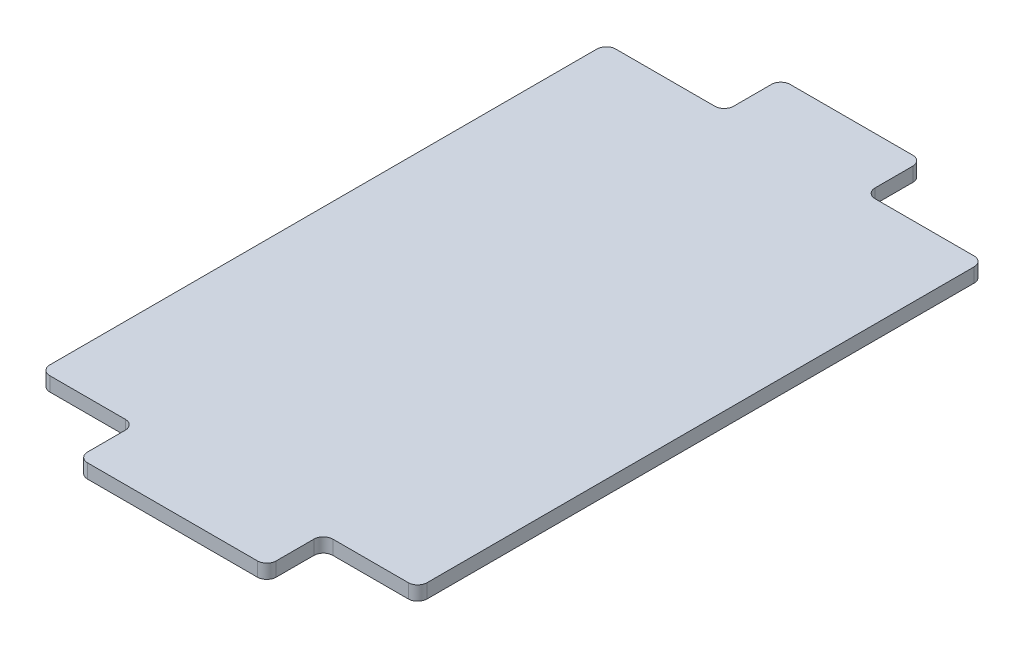
SolidWorks part; units mm, degrees
ref_plane "Спереди" through (0, 0, 0) normal (0, 0, 1) x (1, 0, 0)
ref_plane "Сверху" through (0, 0, 0) normal (0, 1, 0) x (1, 0, 0)
ref_plane "Справа" through (0, 0, 0) normal (1, 0, 0) x (0, 0, -1)
sketch "Эскиз1" plane through (0, 0, 0) normal (0, 1, 0) x (1, 0, 0)
  line L1 (-20, 30) -> (20, 30)
  line L2 (-20, 30) -> (-20, -30)
  line L3 (-20, -30) -> (20, -30)
  line L4 (20, 30) -> (20, -30)
  line L5 (-20, 30) -> (20, -30) construction
  line L6 (-20, -30) -> (20, 30) construction
  point P0 (0, 0)
  dimension "D1" = 60
  dimension "D2" = 40
extrude "Бобышка-Вытянуть1" add sketch "Эскиз1" along normal blind 1.5
sketch "Эскиз2" plane through (0, 1.5, 0) normal (0, 1, 0) x (1, 0, 0)
  line L0 (-20, -30) -> (20, -30) construction
  line L1 (10, -36) -> (-10, -36)
  line L2 (10, -36) -> (10, -30)
  line L3 (10, -30) -> (-10, -30)
  line L4 (-10, -36) -> (-10, -30)
  line L5 (10, -36) -> (-10, -30) construction
  line L6 (10, -30) -> (-10, -36) construction
  line L7 (20, 30) -> (-20, 30) construction
  line L8 (7.5, 36) -> (-7.5, 36)
  line L9 (7.5, 36) -> (7.5, 30)
  line L10 (7.5, 30) -> (-7.5, 30)
  line L11 (-7.5, 36) -> (-7.5, 30)
  line L12 (7.5, 36) -> (-7.5, 30) construction
  line L13 (7.5, 30) -> (-7.5, 36) construction
  point P0 (0, -33)
  point P9 (0, 33)
  point P15 (0, 0)
  dimension "D1" = 6
  dimension "D2" = 20
  dimension "D3" = 6
  dimension "D4" = 15
extrude "Бобышка-Вытянуть2" add sketch "Эскиз2" against normal blind 1.5
fillet "Скругление1" radius 1 12 edges at (-20, 0.75, -30) (20, 0.75, -30) (-20, 0.75, 30) (20, 0.75, 30) (10, 0.75, 30) (10, 0.75, 36) (-10, 0.75, 36) (-10, 0.75, 30) (7.5, 0.75, -30) (7.5, 0.75, -36) (-7.5, 0.75, -36) (-7.5, 0.75, -30)
